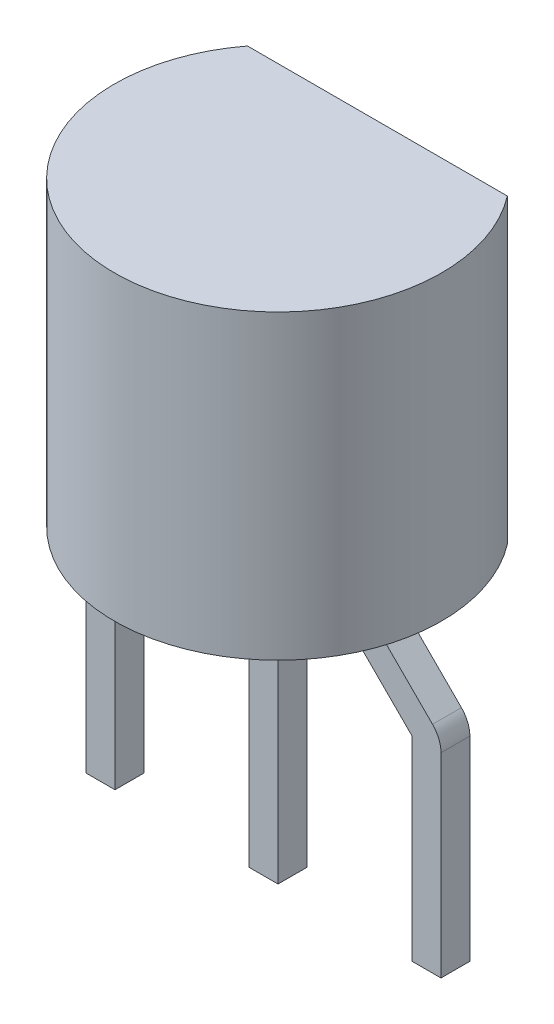
SolidWorks part; units mm, degrees
ref_plane "Front Plane" through (0, 0, 0) normal (0, 0, 1) x (1, 0, 0)
ref_plane "Top Plane" through (0, 0, 0) normal (0, 1, 0) x (1, 0, 0)
ref_plane "Right Plane" through (0, 0, 0) normal (1, 0, 0) x (0, 0, -1)
sketch "Sketch3" plane through (0, 0, 0) normal (0, 1, 0) x (1, 0, 0)
  line L0 (-2.0248, 1.55) -> (2.0248, 1.55)
  circle A0 centre (0, 0) radius 2.55
extrude "Extrude2" add sketch "Sketch3" along normal blind 4.7 contours A0
extrude "Extrude3" cut sketch "Sketch3<3>" along normal through all contours L0 A0 region at (0, 0, -1.9576)
sketch "Sketch3<3>" plane through (0, 0, 0) normal (0, 1, 0) x (1, 0, 0) same geometry as "Sketch3"
sketch "Sketch11" plane through (0, 0, 0) normal (0, -1, 0) x (1, 0, 0)
  line L1 (-0.225, 0.225) -> (0.225, 0.225)
  line L2 (-0.225, 0.225) -> (-0.225, -0.225)
  line L3 (-0.225, -0.225) -> (0.225, -0.225)
  line L4 (0.225, 0.225) -> (0.225, -0.225)
  line L5 (-0.225, 0.225) -> (0.225, -0.225) construction
  line L6 (-0.225, -0.225) -> (0.225, 0.225) construction
  point P0 (0, 0)
sketch "Sketch12" plane through (0, 0, 0) normal (0, -1, 0) x (1, 0, 0)
  line L1 (-1.495, 0.225) -> (-1.045, 0.225)
  line L2 (-1.495, 0.225) -> (-1.495, -0.225)
  line L3 (-1.495, -0.225) -> (-1.045, -0.225)
  line L4 (-1.045, 0.225) -> (-1.045, -0.225)
  line L5 (-1.495, 0.225) -> (-1.045, -0.225) construction
  line L6 (-1.495, -0.225) -> (-1.045, 0.225) construction
  point P0 (-1.27, 0)
sketch "Sketch13" plane through (0, 0, 0) normal (0, -1, 0) x (1, 0, 0)
  line L1 (1.045, 0.225) -> (1.495, 0.225)
  line L2 (1.045, 0.225) -> (1.045, -0.225)
  line L3 (1.045, -0.225) -> (1.495, -0.225)
  line L4 (1.495, 0.225) -> (1.495, -0.225)
  line L5 (1.045, 0.225) -> (1.495, -0.225) construction
  line L6 (1.045, -0.225) -> (1.495, 0.225) construction
  point P0 (1.27, 0)
extrude "Extrude8" add sketch "Sketch13" along normal blind 0.1
extrude "Extrude9" add sketch "Sketch12" along normal blind 0.1
extrude "Extrude10" add sketch "Sketch11" along normal blind 1.5986
sketch "Sketch32" plane through (0, -0.1, 0) normal (0, -1, 0) x (1, 0, 0)
  line L1 (-1.495, 0.225) -> (-1.045, 0.225)
  line L2 (-1.495, 0.225) -> (-1.495, -0.225)
  line L3 (-1.495, -0.225) -> (-1.045, -0.225)
  line L4 (-1.045, 0.225) -> (-1.045, -0.225)
revolve "Revolve4" add sketch "Sketch32" angle 45 about L2
sketch "Sketch34" plane through (-0.7975, -0.7975, 0) normal (-0.7071, -0.7071, 0) x (0, 0, 1)
  line L1 (-0.225, 0.9864) -> (0.225, 0.9864)
  line L2 (-0.225, 0.9864) -> (-0.225, 0.5364)
  line L3 (-0.225, 0.5364) -> (0.225, 0.5364)
  line L4 (0.225, 0.9864) -> (0.225, 0.5364)
extrude "Extrude12" add sketch "Sketch34" along normal blind 1.61
sketch "Sketch36" plane through (-1.9359, -1.9359, 0) normal (-0.7071, -0.7071, 0) x (0, 0, 1)
  line L1 (-0.225, 0.9864) -> (0.225, 0.9864)
  line L2 (-0.225, 0.9864) -> (-0.225, 0.5364)
  line L3 (-0.225, 0.5364) -> (0.225, 0.5364)
  line L4 (0.225, 0.9864) -> (0.225, 0.5364)
revolve "Revolve5" add sketch "Sketch36" angle 45 about L3
sketch "Sketch37" plane through (0, -1.5566, 0) normal (0, -1, 0) x (1, 0, 0)
  line L1 (-2.7652, 0.225) -> (-2.3152, 0.225)
  line L2 (-2.7652, 0.225) -> (-2.7652, -0.225)
  line L3 (-2.7652, -0.225) -> (-2.3152, -0.225)
  line L4 (-2.3152, 0.225) -> (-2.3152, -0.225)
extrude "Extrude13" add sketch "Sketch37" along normal blind 3.04
sketch "Sketch38" plane through (0, -0.1, 0) normal (0, -1, 0) x (1, 0, 0)
  line L1 (1.045, 0.225) -> (1.495, 0.225)
  line L2 (1.045, 0.225) -> (1.045, -0.225)
  line L3 (1.045, -0.225) -> (1.495, -0.225)
  line L4 (1.495, 0.225) -> (1.495, -0.225)
revolve "Revolve6" add sketch "Sketch38" angle 45 about L4 reverse direction yes
sketch "Sketch39" plane through (0.7975, -0.7975, 0) normal (0.7071, -0.7071, 0) x (0, 0, -1)
  line L1 (-0.225, 0.9864) -> (0.225, 0.9864)
  line L2 (-0.225, 0.9864) -> (-0.225, 0.5364)
  line L3 (-0.225, 0.5364) -> (0.225, 0.5364)
  line L4 (0.225, 0.9864) -> (0.225, 0.5364)
extrude "Extrude14" add sketch "Sketch39" along normal blind 1.61
sketch "Sketch40" plane through (1.9359, -1.9359, 0) normal (0.7071, -0.7071, 0) x (0, 0, -1)
  line L0 (-0.225, 0.5364) -> (0.225, 0.5364) construction
  line L1 (-0.225, 0.9864) -> (0.225, 0.9864)
  line L2 (-0.225, 0.9864) -> (-0.225, 0.5364)
  line L3 (-0.225, 0.5364) -> (0.225, 0.5364)
  line L4 (0.225, 0.9864) -> (0.225, 0.5364)
revolve "Revolve7" add sketch "Sketch40" angle 45 about L3
sketch "Sketch41" plane through (0, -1.5566, 0) normal (0, -1, 0) x (1, 0, 0)
  line L1 (2.3152, 0.225) -> (2.7652, 0.225)
  line L2 (2.3152, 0.225) -> (2.3152, -0.225)
  line L3 (2.3152, -0.225) -> (2.7652, -0.225)
  line L4 (2.7652, 0.225) -> (2.7652, -0.225)
extrude "Extrude15" add sketch "Sketch41" along normal blind 3.04
sketch "Sketch42" plane through (0, -1.5986, 0) normal (0, -1, 0) x (1, 0, 0)
  line L1 (-0.225, 0.225) -> (0.225, 0.225)
  line L2 (-0.225, 0.225) -> (-0.225, -0.225)
  line L3 (-0.225, -0.225) -> (0.225, -0.225)
  line L4 (0.225, 0.225) -> (0.225, -0.225)
extrude "Extrude16" add sketch "Sketch42" along normal blind 3
